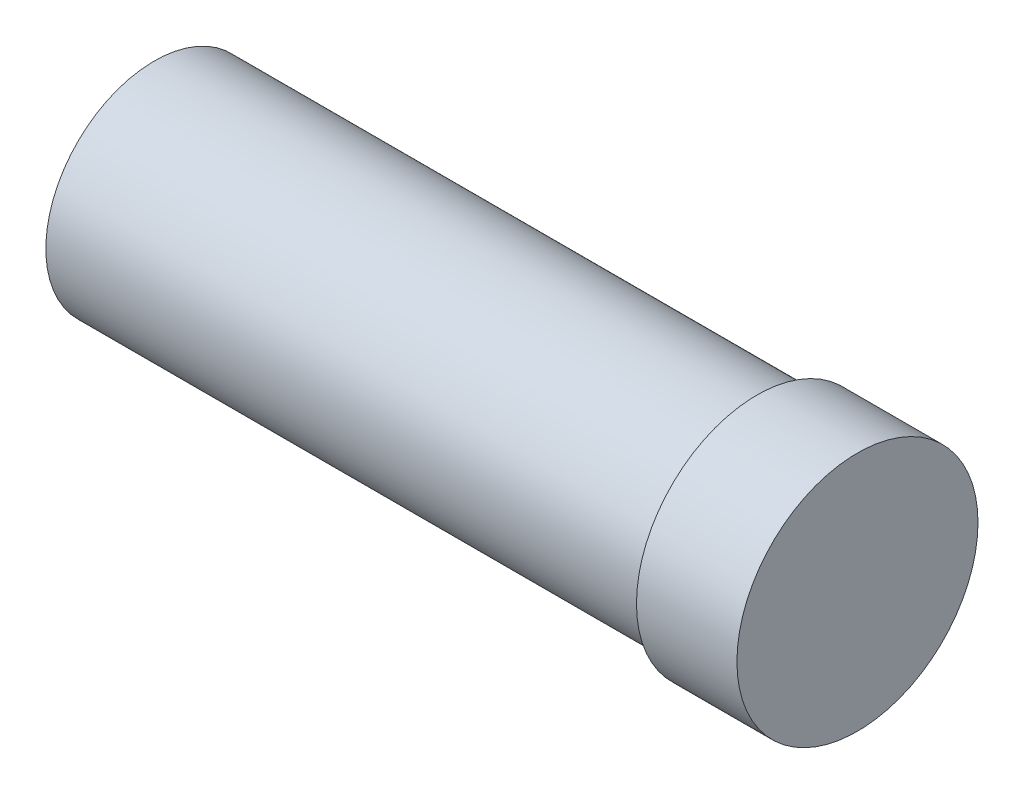
SolidWorks part; units mm, degrees
material "AISI 304"
ref_plane "Front Plane" through (0, 0, 0) normal (0, 0, 1) x (1, 0, 0)
ref_plane "Top Plane" through (0, 0, 0) normal (0, 1, 0) x (1, 0, 0)
ref_plane "Right Plane" through (0, 0, 0) normal (1, 0, 0) x (0, 0, -1)
sketch "Sketch2" plane through (0, 0, 0) normal (1, 0, 0) x (0, 0, -1)
  circle A0 centre (0, 0) radius 27
extrude "Boss-Extrude1" add sketch "Sketch2" along normal blind 150
sketch "Sketch3" plane through (150, 0, 0) normal (1, 0, 0) x (0, 0, -1)
  circle A0 centre (0, 0) radius 30
extrude "Boss-Extrude2" add sketch "Sketch3" along normal blind 25
